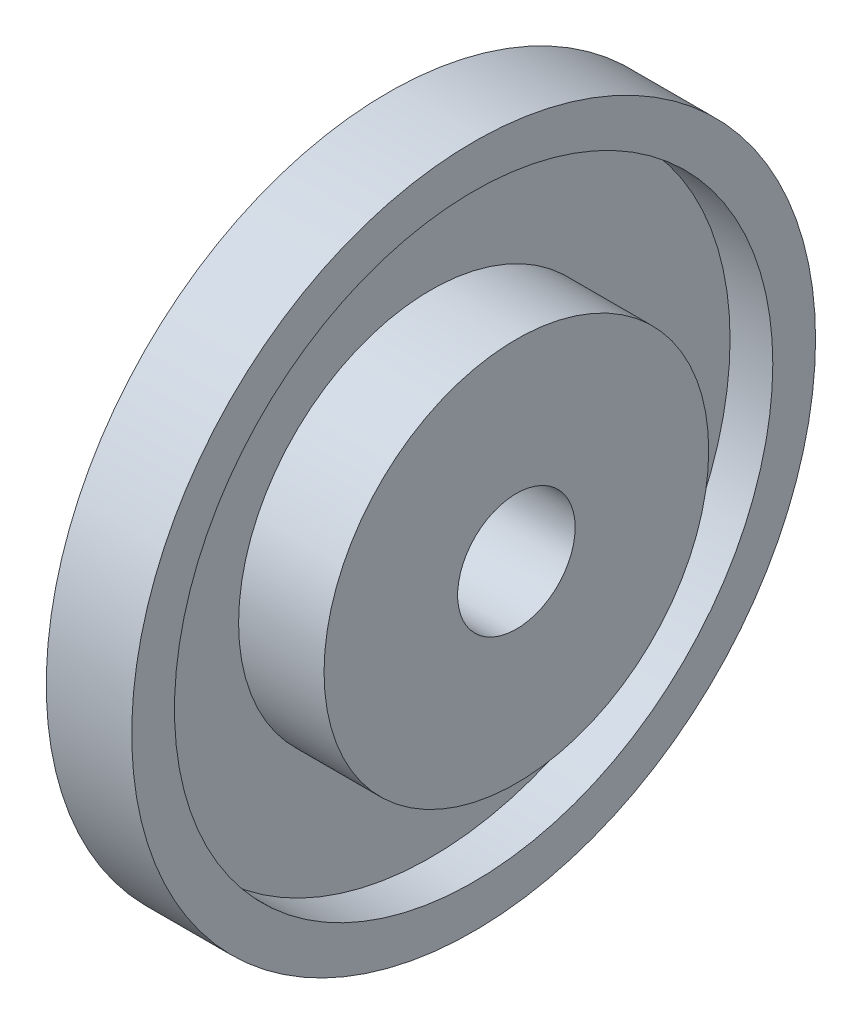
SolidWorks part; units mm, degrees
ref_plane "前视基准面" through (0, 0, 0) normal (0, 0, 1) x (1, 0, 0)
ref_plane "上视基准面" through (0, 0, 0) normal (0, 1, 0) x (1, 0, 0)
ref_plane "右视基准面" through (0, 0, 0) normal (1, 0, 0) x (0, 0, -1)
sketch "草图1" plane through (0, 0, 0) normal (1, 0, 0) x (0, 0, -1)
  circle A0 centre (0, 0) radius 2.75
  circle A1 centre (0, 0) radius 9
  circle A2 centre (0, 0) radius 14
  circle A3 centre (0, 0) radius 16
  dimension "D1" = 5.5
  dimension "D2" = 18
  dimension "D3" = 32
  dimension "D4" = 28
extrude "凸台-拉伸1" add sketch "草图1" along normal blind 2 contours A2 A1 region at (0, 0, 13.604)
extrude "凸台-拉伸2" add sketch "草图1<3>" along normal blind 4 contours A3 A2 region at (0, 0, 15.5475)
sketch "草图1<3>" plane through (0, 0, 0) normal (1, 0, 0) x (0, 0, -1) same geometry as "草图1"
extrude "凸台-拉伸3" add sketch "草图1<4>" along normal blind 6 contours A1 A0 region at (0, 0, 8.7454)
sketch "草图1<4>" plane through (0, 0, 0) normal (1, 0, 0) x (0, 0, -1) same geometry as "草图1"
chamfer "倒角1" distance 2 angle 60 1 edges at (0, 0, -2.75) first distance on face at (6, 0, -2.75)
